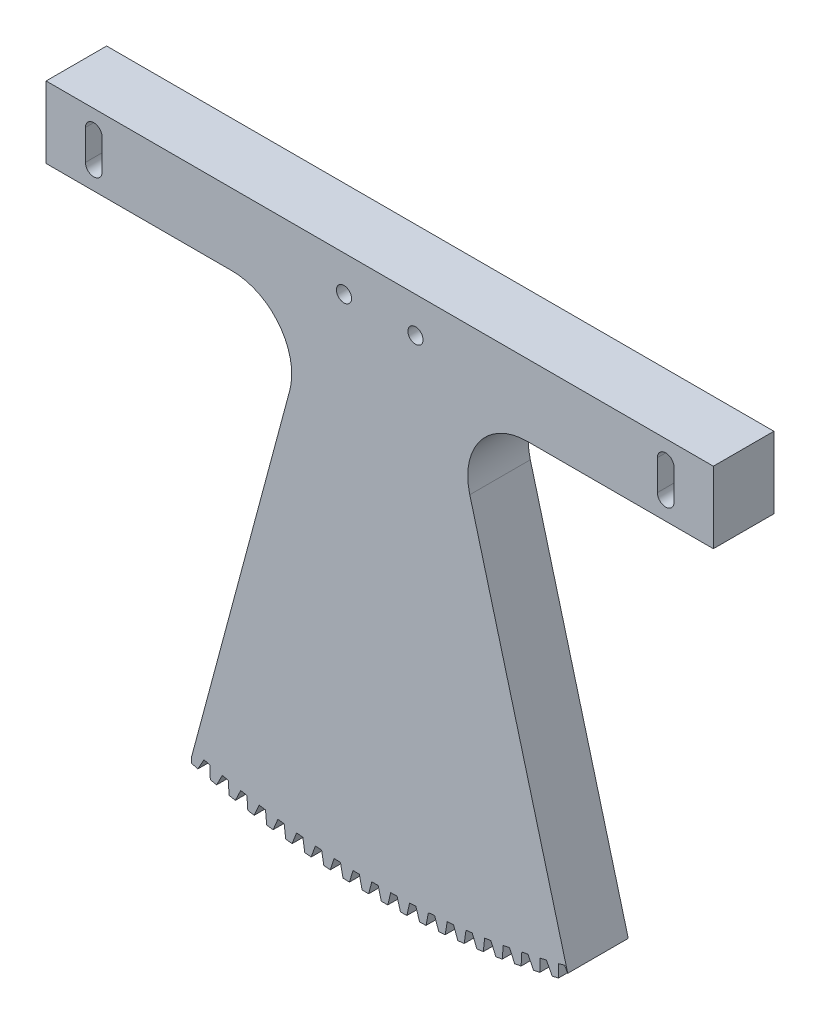
SolidWorks part; units mm, degrees
ref_plane "Front Plane" through (0, 0, 0) normal (0, 0, 1) x (1, 0, 0)
ref_plane "Top Plane" through (0, 0, 0) normal (0, 1, 0) x (1, 0, 0)
ref_plane "Right Plane" through (0, 0, 0) normal (1, 0, 0) x (0, 0, -1)
sketch "Sketch3" plane through (0, 0, 0) normal (0, 0, 1) x (1, 0, 0)
  line L0 (0, 0) -> (0, -304.8) construction
  line L1 (-21.234, -79.2464) -> (-78.888, -294.4142)
  line L2 (21.234, -79.2464) -> (78.888, -294.4142)
  line L4 (-140, -79.56) -> (140, -79.56)
  line L5 (-140, -79.56) -> (-140, -109.56)
  line L6 (-140, -109.56) -> (140, -109.56)
  line L7 (140, -79.56) -> (140, -109.56)
  line L8 (0, -109.56) -> (0, -79.56) construction
  line L9 (-140, -94.56) -> (140, -94.56) construction
  arc A0 (-78.888, -294.4142) -> (78.888, -294.4142) centre (0, 0) ccw
  point P269 (0, -94.56)
  dimension "D1" = 304.8
  dimension "D4" = 79.56
  dimension "D5" = 30
  dimension "D6" = 280
  dimension "D7" = 140
extrude "Boss-Extrude2" add sketch "Sketch3" along normal blind 25.4 contours L7 L4 L2 L6 | L1 L6 L2 L4 | L1 L4 L2 | L5 L6 L1 L4 | L1 A0 L2 L6 region at (0, -95.3531, 0) region at (-82.6452, -94.3847, 0) region at (0, -220.3694, 0) region at (82.6452, -94.3847, 0)
fillet "Fillet1" radius 25 2 edges at (-29.3565, -109.56, 12.7) (29.3565, -109.56, 12.7)
sketch "Sketch4" plane through (0, -79.56, 0) normal (0, 1, 0) x (1, 0, 0)
  line L1 (-140, 0) -> (140, 0)
  line L2 (-140, 0) -> (-140, -25.4)
  line L3 (-140, -25.4) -> (140, -25.4)
  line L4 (140, 0) -> (140, -25.4)
  line L5 (0, -25.4) -> (0, 0) construction
  line L6 (-140, -12.7) -> (140, -12.7) construction
  point P252 (0, -12.7)
sketch "Sketch5" plane through (0, 0, 0) normal (0, 0, -1) x (-1, 0, 0)
  line L0 (-123.5, -94.56) -> (-123.5, -100.91)
  line L1 (-116.5, -94.56) -> (-116.5, -100.91)
  line L2 (116.5, -94.56) -> (116.5, -88.21)
  line L3 (140, -79.56) -> (-140, -79.56) construction
  line L4 (-120, -88.21) -> (-120, -100.91) construction
  line L5 (0, -79.56) -> (0, -109.56) construction
  line L6 (-116.5, -94.56) -> (-116.5, -88.21)
  line L7 (-123.5, -94.56) -> (-123.5, -88.21)
  line L8 (116.5, -94.56) -> (116.5, -100.91)
  line L9 (123.5, -94.56) -> (123.5, -100.91)
  line L10 (123.5, -94.56) -> (123.5, -88.21)
  line L11 (-140, -79.56) -> (-140, -109.56) construction
  line L12 (120, -88.21) -> (120, -100.91) construction
  arc A1 (-116.5, -88.21) -> (-123.5, -88.21) centre (-120, -88.21) ccw
  arc A2 (-123.5, -100.91) -> (-116.5, -100.91) centre (-120, -100.91) ccw
  arc A3 (123.5, -100.91) -> (116.5, -100.91) centre (120, -100.91) cw
  arc A4 (116.5, -88.21) -> (123.5, -88.21) centre (120, -88.21) cw
  circle A5 centre (-15, -94.56) radius 3.175
  circle A6 centre (15, -94.56) radius 3.175
  dimension "D1" = 16.5
  dimension "D2" = 7
  dimension "D3" = 8.65
  dimension "D5" = 3.5
  dimension "D6" = 15
  dimension "D8" = 6.35
  dimension "D4" = 6.35
  dimension "D7" = 15
sketch "Sketch13" plane through (0, 0, 0) normal (0, 0, -1) x (-1, 0, 0)
  line L0 (0, 0) -> (78.888, -294.4142)
  line L1 (0, 0) -> (-78.888, -294.4142)
  arc A0 (-78.888, -294.4142) -> (78.888, -294.4142) centre (0, 0) ccw
  arc A1 (-78.888, -294.4142) -> (78.888, -294.4142) centre (0, 0) ccw construction
  arc A2 (-78.888, -294.4142) -> (78.888, -294.4142) centre (0, 0) ccw
  circle A3 centre (0, 0) radius 304.8
  dimension "D1" = 609.6
sketch "Sketch14" plane through (0, 0, 0) normal (0, 0, -1) x (-1, 0, 0)
  line L0 (0, 0) -> (80.0203, -298.6399) construction
  line L2 (78.888, -294.4142) -> (78.9109, -297.0369)
  line L3 (78.9109, -297.0369) -> (76.2891, -297.7211)
  line L18 (76.2891, -297.7211) -> (75.0275, -295.4216)
  line L20 (0, 0) -> (-79.2746, -295.8555) construction
  line L32 (78.888, -294.4142) -> (75.0275, -295.4216)
  line L33 (75.0275, -295.4216) -> (78.888, -294.4142)
  line L34 (0, 0) -> (-75.3952, -296.8678) construction
  line L35 (0, 0) -> (-71.5028, -297.8293) construction
  line L36 (0, 0) -> (-67.5982, -298.7397) construction
  line L37 (0, 0) -> (-63.6821, -299.5989) construction
  line L38 (0, 0) -> (-59.755, -300.4068) construction
  line L39 (0, 0) -> (-55.8176, -301.1633) construction
  line L40 (0, 0) -> (-51.8707, -301.8681) construction
  line L41 (0, 0) -> (-47.9149, -302.5212) construction
  line L42 (0, 0) -> (-43.951, -303.1225) construction
  line L43 (0, 0) -> (-39.9794, -303.6718) construction
  line L44 (0, 0) -> (-36.0011, -304.1691) construction
  line L45 (0, 0) -> (-32.0165, -304.6143) construction
  line L46 (0, 0) -> (-28.0265, -305.0073) construction
  line L47 (0, 0) -> (-24.0316, -305.348) construction
  line L48 (0, 0) -> (-20.0327, -305.6364) construction
  line L49 (0, 0) -> (-16.0303, -305.8724) construction
  line L50 (0, 0) -> (-12.0252, -306.0561) construction
  line L51 (0, 0) -> (-8.018, -306.1873) construction
  line L52 (0, 0) -> (-4.0094, -306.266) construction
  line L53 (0, 0) -> (-0.0002, -306.2922) construction
  line L54 (0, 0) -> (4.0091, -306.266) construction
  line L55 (0, 0) -> (8.0176, -306.1873) construction
  line L56 (0, 0) -> (12.0248, -306.0561) construction
  line L57 (0, 0) -> (16.03, -305.8725) construction
  line L58 (0, 0) -> (20.0323, -305.6364) construction
  line L59 (0, 0) -> (24.0313, -305.348) construction
  line L60 (0, 0) -> (28.0261, -305.0073) construction
  line L61 (0, 0) -> (32.0162, -304.6143) construction
  line L62 (0, 0) -> (36.0007, -304.1691) construction
  line L63 (0, 0) -> (39.9791, -303.6719) construction
  line L64 (0, 0) -> (43.9506, -303.1225) construction
  line L65 (0, 0) -> (47.9146, -302.5213) construction
  line L66 (0, 0) -> (51.8704, -301.8682) construction
  line L67 (0, 0) -> (55.8173, -301.1633) construction
  line L68 (0, 0) -> (59.7546, -300.4069) construction
  line L69 (0, 0) -> (63.6817, -299.599) construction
  line L70 (0, 0) -> (67.5979, -298.7398) construction
  line L71 (0, 0) -> (71.5025, -297.8293) construction
  line L72 (0, 0) -> (75.3948, -296.8679) construction
  line L73 (0, 0) -> (-79.2746, -295.8555) construction
  line L74 (0, 0) -> (-75.3952, -296.8678) construction
  line L137 (37.789, -141.0305) -> (78.888, -294.4142) construction
  line L138 (-140, -79.56) -> (-140, -109.56)
  line L139 (-140, -109.56) -> (-61.9371, -109.56)
  line L140 (-37.789, -141.0305) -> (-78.888, -294.4142)
  line L141 (78.888, -294.4142) -> (37.789, -141.0305)
  line L142 (61.9371, -109.56) -> (140, -109.56)
  line L143 (140, -109.56) -> (140, -79.56)
  line L144 (140, -79.56) -> (-140, -79.56)
  line L145 (-140, -79.56) -> (-140, -109.56)
  line L146 (-140, -109.56) -> (-61.9371, -109.56)
  line L147 (-37.789, -141.0305) -> (-78.888, -294.4142)
  line L149 (61.9371, -109.56) -> (140, -109.56)
  line L150 (140, -109.56) -> (140, -79.56)
  line L151 (140, -79.56) -> (-140, -79.56)
  circle A0 centre (0, 0) radius 307.34
  circle A1 centre (0, 0) radius 302.26
  arc A3 (-37.789, -141.0305) -> (-61.9371, -109.56) centre (-61.9371, -134.56) ccw
  arc A5 (61.9371, -109.56) -> (37.789, -141.0305) centre (61.9371, -134.56) ccw
  arc A6 (-37.789, -141.0305) -> (-61.9371, -109.56) centre (-61.9371, -134.56) ccw
  arc A8 (61.9371, -109.56) -> (37.789, -141.0305) centre (61.9371, -134.56) ccw
  arc A11 (-78.888, -294.4142) -> (78.888, -294.4142) centre (0, 0) ccw
  arc A12 (-78.888, -294.4142) -> (78.888, -294.4142) centre (0, 0) ccw
  arc M181 (-78.888, -294.4142) -> (78.888, -294.4142) centre (0, 0) ccw
  dimension "D5" = 614.68
  dimension "D6" = 30
  dimension "D7" = 40
  dimension "D4" = 604.52
  dimension "D1" = 14.5
  dimension "D3" = 14.5
  dimension "D8" = 0.75
  dimension "D9" = 306.2922
  dimension "D10" = 0.75
  dimension "D2" = 0
extrude "Boss-Extrude4" add sketch "Sketch14" against normal up to surface (25.4 mm away) contours L2 M181 region at (-77.2591, -296.0724, 0) up to face at (0, -146.6727, 25.4)
sketch "Sketch15" plane through (0, 0, 0) normal (1, 0, 0) x (0, 0, -1)
  line L0 (0, 0) -> (-23.3364, 0) construction
sketch "Sketch16" plane through (0, 0, 0) normal (0, 0, -1) x (-1, 0, 0)
  line L0 (75.0275, -295.4216) -> (73.7653, -293.1208)
  line L1 (73.7653, -293.1208) -> (71.1999, -293.7544)
  line L2 (71.1999, -293.7544) -> (71.1541, -296.3784)
  line L3 (0, 0) -> (71.5025, -297.8293) construction
  line L4 (0, 0) -> (75.3948, -296.8679) construction
  circle A0 centre (0, 0) radius 302.26 construction
  arc A1 (-78.888, -294.4142) -> (78.888, -294.4142) centre (0, 0) ccw construction
  dimension "D1" = 14.5
  dimension "D2" = 14.5
extrude "Cut-Extrude2" cut sketch "Sketch16" against normal through all and the other way through all
pattern_circular "CirPattern8" count 20 every 1.5 about axis through (0, 0, 0) along (0, 0, 1) of "Cut-Extrude2", "Boss-Extrude4"
extrude "Cut-Extrude3" cut sketch "Sketch5" against normal through all
equation "\"D7@Sketch3\"=\"D6@Sketch3\"/2"
